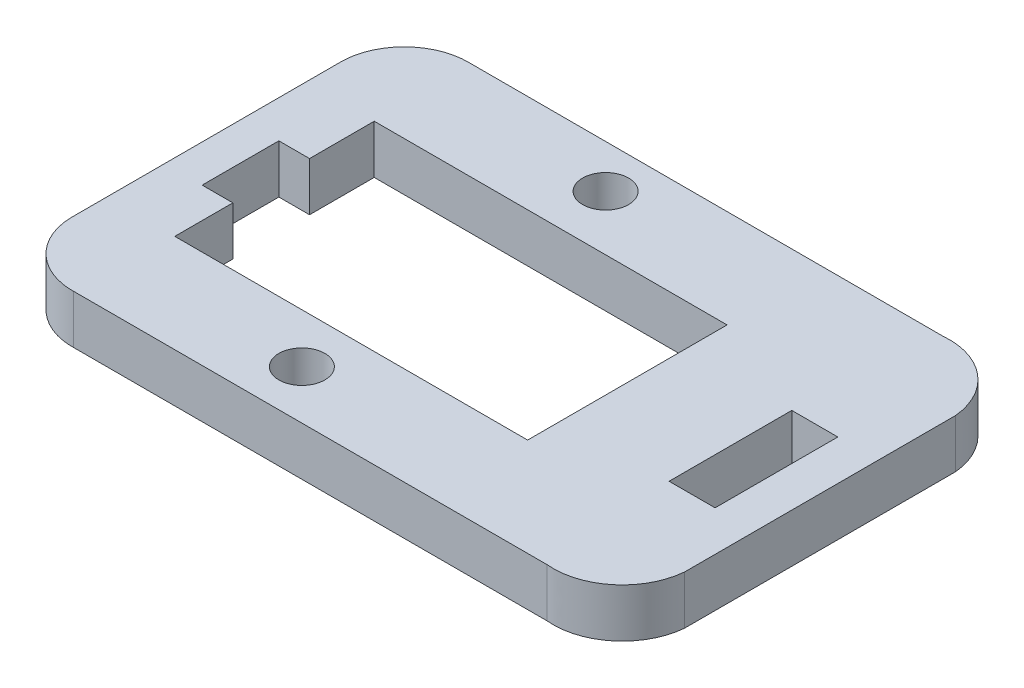
SolidWorks part; units mm, degrees
ref_plane "Front Plane" through (0, 0, 0) normal (0, 0, 1) x (1, 0, 0)
ref_plane "Top Plane" through (0, 0, 0) normal (0, 1, 0) x (1, 0, 0)
ref_plane "Right Plane" through (0, 0, 0) normal (1, 0, 0) x (0, 0, -1)
sketch "Sketch1" plane through (0, 0, 0) normal (0, 1, 0) x (1, 0, 0)
  line L0 (-15.5612, 6.5) -> (7.4388, 6.5)
  line L1 (7.4388, 6.5) -> (7.4388, -6.5)
  line L2 (7.4388, -6.5) -> (-15.5612, -6.5)
  line L3 (-15.5612, -6.5) -> (-15.5612, -2.7163)
  line L4 (-15.5612, -2.7163) -> (-17.5613, -2.7163)
  line L5 (-17.5613, -2.7163) -> (-17.5613, 2.2836)
  line L6 (-17.5613, 2.2836) -> (-15.5612, 2.2836)
  line L7 (-15.5612, 2.2836) -> (-15.5612, 6.5)
  line L8 (-15.7526, 12.8991) -> (15.1125, 12.8991)
  line L9 (20, 8.8318) -> (20, -8.8318)
  line L10 (15.1125, -12.8991) -> (-15.7526, -12.8991)
  line L11 (-20, -8.8318) -> (-20, 8.8318)
  line L12 (14.3743, 3.7836) -> (17.3744, 3.7836)
  line L13 (17.3744, 3.7836) -> (17.3744, -4.2164)
  line L14 (17.3744, -4.2164) -> (14.3743, -4.2164)
  line L15 (14.3743, -4.2164) -> (14.3743, 3.7836)
  line L16 (-5.5619, 10.0836) -> (-2.562, 10.0836) construction
  line L17 (-4.0619, 11.5836) -> (-4.0619, 8.5836) construction
  line L18 (-4.0619, -8.2163) -> (-4.0619, -11.2164) construction
  line L19 (-2.562, -9.7164) -> (-5.5619, -9.7163) construction
  circle A0 centre (-4.0619, 10.0836) radius 1.5
  circle A1 centre (-4.0619, -9.7163) radius 1.5
  spline S8 degree 3 poles (15.1125, 12.8991) (17.5751, 13.1246) (19.7745, 11.2944) (20, 8.8318) knots 0.111111 0.111111 0.111111 0.111111 0.222222 0.222222 0.222222 0.222222
  spline S9 degree 3 poles (20, -8.8318) (19.7745, -11.2944) (17.5751, -13.1246) (15.1125, -12.8991) knots 0.333333 0.333333 0.333333 0.333333 0.444444 0.444444 0.444444 0.444444
  spline S10 degree 3 poles (-15.7526, -12.8991) (-18.0392, -12.9487) (-19.9505, -11.1184) (-20, -8.8318) knots 0.555556 0.555556 0.555556 0.555556 0.666667 0.666667 0.666667 0.666667
  spline S11 degree 3 poles (-20, 8.8318) (-19.9505, 11.1184) (-18.0392, 12.9487) (-15.7526, 12.8991) knots 0.777778 0.777778 0.777778 0.777778 1 1 1 1
  dimension "D1" = 2.9999
  dimension "D2" = 7.4388
  dimension "D3" = 14.3743
  dimension "D4" = 15.1125
  dimension "D5" = 17.3744
  dimension "D6" = 20
  dimension "D7" = 4.0619
  dimension "D8" = 2.2836
  dimension "D9" = 15.5612
  dimension "D10" = 15.7526
  dimension "D11" = 17.5613
  dimension "D12" = 20
  dimension "D13" = 3.7836
  dimension "D14" = 6.5
  dimension "D15" = 8.8318
  dimension "D16" = 10.0836
  dimension "D17" = 12.8991
  dimension "D18" = 2.7163
  dimension "D19" = 4.2164
  dimension "D20" = 6.5
  dimension "D21" = 8.8317
  dimension "D22" = 9.7163
  dimension "D23" = 12.8991
extrude "Boss-Extrude1" add sketch "Sketch1" along normal blind 3.175
